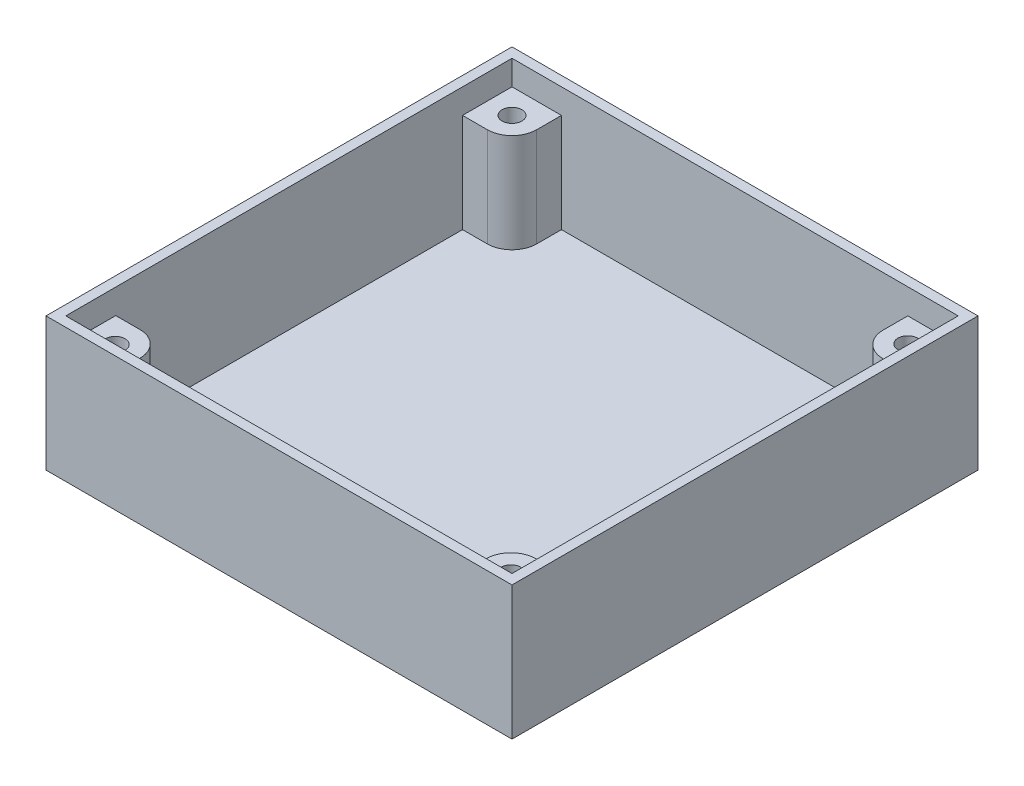
SolidWorks part; units mm, degrees
ref_plane "Front Plane" through (0, 0, 0) normal (0, 0, 1) x (1, 0, 0)
ref_plane "Top Plane" through (0, 0, 0) normal (0, 1, 0) x (1, 0, 0)
ref_plane "Right Plane" through (0, 0, 0) normal (1, 0, 0) x (0, 0, -1)
sketch "Sketch1" plane through (0, 0, 0) normal (0, 1, 0) x (1, 0, 0)
  line L1 (-47.1, -47.1) -> (47.1, -47.1)
  line L2 (-47.1, -47.1) -> (-47.1, 47.1)
  line L3 (-47.1, 47.1) -> (47.1, 47.1)
  line L4 (47.1, -47.1) -> (47.1, 47.1)
  line L5 (-47.1, -47.1) -> (47.1, 47.1) construction
  line L6 (-47.1, 47.1) -> (47.1, -47.1) construction
  point P0 (0, 0)
  dimension "D1" = 94.2
  dimension "D2" = 94.2
extrude "Boss-Extrude1" add sketch "Sketch1" along normal blind 2
sketch "Sketch2" plane through (0, 2, 0) normal (0, 1, 0) x (1, 0, 0)
  line L4 (47.1, -47.1) -> (47.1, 47.1)
  line L5 (47.1, 47.1) -> (-47.1, 47.1)
  line L6 (-47.1, 47.1) -> (-47.1, -47.1)
  line L7 (-47.1, -47.1) -> (47.1, -47.1)
  line L8 (47.1, -47.1) -> (47.1, 47.1)
  line L9 (47.1, 47.1) -> (-47.1, 47.1)
  line L10 (-47.1, 47.1) -> (-47.1, -47.1)
  line L11 (-47.1, -47.1) -> (47.1, -47.1)
  line L16 (45.1, -45.1) -> (45.1, 45.1)
  line L17 (45.1, 45.1) -> (-45.1, 45.1)
  line L18 (-45.1, 45.1) -> (-45.1, -45.1)
  line L19 (-45.1, -45.1) -> (45.1, -45.1)
  line L20 (45.1, -45.1) -> (45.1, 45.1)
  line L21 (45.1, 45.1) -> (-45.1, 45.1)
  line L22 (-45.1, 45.1) -> (-45.1, -45.1)
  line L23 (-45.1, -45.1) -> (45.1, -45.1)
  dimension "D1" = 0
  dimension "D2" = 2
extrude "Boss-Extrude2" add sketch "Sketch2" along normal blind 25
sketch "Sketch3" plane through (0, 2, 0) normal (0, 1, 0) x (1, 0, 0)
  line L1 (-45.1, 45.1) -> (-35.1, 45.1)
  line L2 (-45.1, 45.1) -> (-45.1, 35.1)
  line L3 (-45.1, 35.1) -> (-40.1, 35.1)
  line L4 (-35.1, 45.1) -> (-35.1, 40.1)
  line L29 (45, 45) -> (45, 35)
  line L30 (45, 45) -> (35, 45)
  line L31 (35, 45) -> (35, 40)
  line L32 (45, 35) -> (40, 35)
  line L33 (44.9, -45.1) -> (34.9, -45.1)
  line L34 (44.9, -45.1) -> (44.9, -35.1)
  line L35 (44.9, -35.1) -> (39.9, -35.1)
  line L36 (34.9, -45.1) -> (34.9, -40.1)
  line L37 (-45.2, -45) -> (-45.2, -35)
  line L38 (-45.2, -45) -> (-35.2, -45)
  line L39 (-35.2, -45) -> (-35.2, -40)
  line L40 (-45.2, -35) -> (-40.2, -35)
  arc A0 (-40.1, 35.1) -> (-35.1, 40.1) centre (-40.1, 40.1) ccw
  arc A7 (35, 40) -> (40, 35) centre (40, 40) ccw
  arc A8 (39.9, -35.1) -> (34.9, -40.1) centre (39.9, -40.1) ccw
  arc A9 (-35.2, -40) -> (-40.2, -35) centre (-40.2, -40) ccw
  point P7 (-35.1, 35.1)
  point P29 (3.5, 0)
  point P30 (-1, 0)
  point P31 (0.5, 0)
  point P32 (-0.1, 0)
  dimension "D3" = 5
  dimension "D1" = 10
  dimension "D2" = 10
  dimension "D4" = 4
extrude "Boss-Extrude3" add sketch "Sketch3" along normal blind 20
sketch "Sketch4" plane through (0, 22, 0) normal (0, 1, 0) x (1, 0, 0)
  line L0 (0, 0) -> (16.374, 0) construction
  line L4 (-45.1, 45.1) -> (-45.1, 35.1)
  line L5 (-45.1, 35.1) -> (-40.1, 35.1)
  line L6 (-35.1, 40.1) -> (-35.1, 45.1)
  line L7 (-35.1, 45.1) -> (-45.1, 45.1)
  line L8 (-45.1, 45.1) -> (-45.1, 35.1) construction
  line L9 (-45.1, 35.1) -> (-40.1, 35.1) construction
  line L10 (-35.1, 40.1) -> (-35.1, 45.1) construction
  line L11 (-35.1, 45.1) -> (-45.1, 45.1) construction
  circle A0 centre (-40.1, 40.1) radius 2
  arc A1 (-40.1, 35.1) -> (-35.1, 40.1) centre (-40.1, 40.1) ccw
  arc A2 (-40.1, 35.1) -> (-35.1, 40.1) centre (-40.1, 40.1) ccw construction
  circle A18 centre (39.9, 40.1) radius 2
  circle A21 centre (39.9, -39.9) radius 2 [skipped]
  circle A22 centre (-40.1, -39.9) radius 2 [skipped]
  circle A23 centre (39.9, -40.1) radius 2
  circle A24 centre (-40.1, -40.1) radius 2
  point P16 (-0.1, 0.1)
  point P17 (-0.1, 0)
  point P18 (0, 0)
  point P19 (-0.1, 0.1)
  dimension "D2" = 4
  dimension "D4" = 40
  dimension "D5" = 40
  dimension "D6" = 40
  dimension "D7" = 80.2
  dimension "D1" = 0
  dimension "D3" = 4
extrude "Cut-Extrude1" cut sketch "Sketch4" against normal up to surface (20 mm away) up to face at (39.7929, 2, -39.7929)
